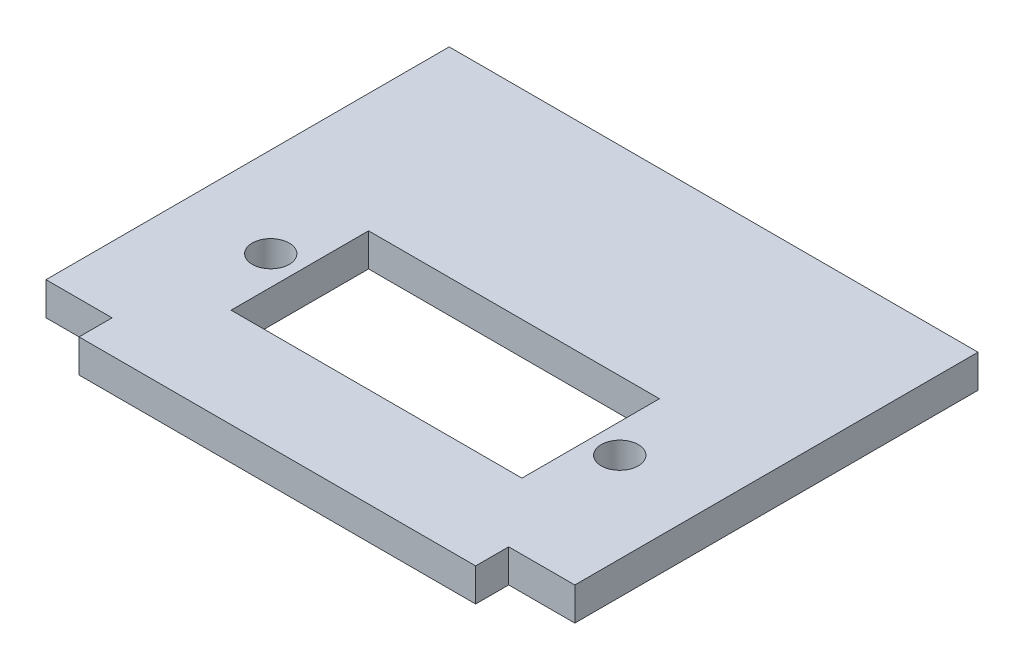
SolidWorks part; units mm, degrees
ref_plane "Front" through (0, 0, 0) normal (0, 0, 1) x (1, 0, 0)
ref_plane "Top" through (0, 0, 0) normal (0, 1, 0) x (1, 0, 0)
ref_plane "Right" through (0, 0, 0) normal (1, 0, 0) x (0, 0, -1)
sketch "Tilt Mount Sketch" plane through (0, 0, 0) normal (0, 1, 0) x (1, 0, 0)
  line L0 (44.45, 0) -> (50.8, 0)
  line L1 (0, 0) -> (6.35, 0)
  line L2 (0, 0) -> (0, 38.7326)
  line L3 (0, 38.7326) -> (50.8, 38.7326)
  line L4 (50.8, 0) -> (50.8, 38.7326)
  line L6 (6.35, 0) -> (6.35, -3.175)
  line L7 (6.35, -3.175) -> (44.45, -3.175)
  line L8 (44.45, 0) -> (44.45, -3.175)
  dimension "D1" = 50.8
  dimension "D2" = 38.1
  dimension "D3" = 3.175
extrude "Tilt Mount" add sketch "Tilt Mount Sketch" along normal blind 3.175
sketch "Servo Hole Sketch" plane through (0, 3.175, 0) normal (0, 1, 0) x (1, 0, 0)
  line L0 (0, 0) -> (50.8, 0) construction
  line L1 (39.37, 6.35) -> (11.43, 6.35)
  line L2 (39.37, 6.35) -> (39.37, 19.558)
  line L3 (39.37, 19.558) -> (11.43, 19.558)
  line L4 (11.43, 6.35) -> (11.43, 19.558)
  line L5 (11.43, 19.558) -> (0, 19.558) construction
  line L6 (0, 38.7326) -> (0, 0) construction
  line L7 (39.37, 19.558) -> (50.8, 19.558) construction
  line L8 (50.8, 0) -> (50.8, 38.7326) construction
  point P14 (0, 0)
  point P15 (0, 0)
  dimension "D1" = 27.94
  dimension "D2" = 13.208
  dimension "D3" = 6.35
sketch "Mounting Holes Guide Sketch" plane through (0, 3.175, 0) normal (0, 1, 0) x (1, 0, 0)
  line L0 (11.43, 19.558) -> (0, 19.558) construction
  line L2 (5.207, 19.558) -> (5.207, 6.35) construction
  line L3 (5.207, 6.35) -> (45.593, 6.35) construction
  line L4 (45.593, 19.558) -> (45.593, 6.35) construction
  line L5 (11.43, 19.558) -> (5.207, 19.558) construction
  line L6 (39.37, 19.558) -> (45.593, 19.558) construction
  line L7 (5.207, 12.954) -> (45.593, 12.954) construction
  line L8 (25.4, 19.558) -> (25.4, 6.35) construction
  line L9 (39.37, 19.558) -> (11.43, 19.558) construction
  line L10 (11.43, 6.35) -> (11.43, 19.558) construction
  circle A0 centre (8.636, 12.954) radius 1.778
  circle A1 centre (42.164, 12.954) radius 1.778
  dimension "D2" = 3.556
  dimension "D3" = 2.794
  dimension "D1" = 40.386
extrude "Servo Hole" cut sketch "Servo Hole Sketch" against normal through all
extrude "Mounting Holes" cut sketch "Mounting Holes Guide Sketch" against normal through all
